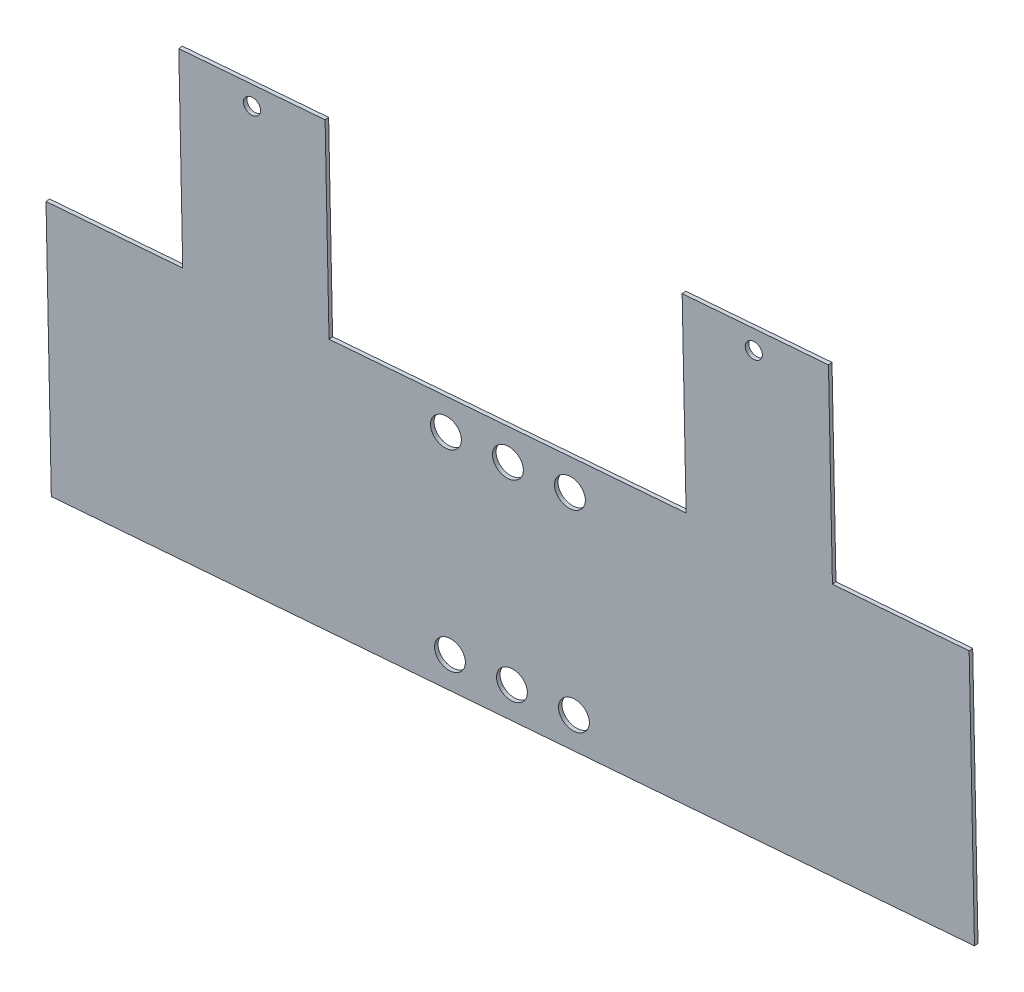
SolidWorks part; units mm, degrees
ref_plane "Front Plane" through (0, 0, 0) normal (0, 0, 1) x (1, 0, 0)
ref_plane "Top Plane" through (0, 0, 0) normal (0, 1, 0) x (1, 0, 0)
ref_plane "Right Plane" through (0, 0, 0) normal (1, 0, 0) x (0, 0, -1)
sketch "Sketch1" plane through (16.9972, -4.1499, 204.6314) normal (-0.0828, 0.0202, -0.9964) x (0.9966, 0.002, -0.0827)
  line L0 (-405.6316, 283.217) -> (-385.6926, 283.217)
  line L1 (-520.3126, 323.857) -> (-500.3736, 323.857)
  line L2 (-520.3126, 323.857) -> (-520.3126, 283.217)
  line L3 (-520.3126, 283.217) -> (-500.3736, 283.217)
  line L4 (-385.6926, 323.857) -> (-385.6926, 283.217)
  line L6 (-426.9676, 283.217) -> (-426.9676, 253.0016)
  line L7 (-426.9676, 253.0016) -> (-405.6316, 253.0016)
  line L8 (-405.6316, 283.217) -> (-405.6316, 253.0016)
  line L9 (-405.0144, 323.857) -> (-385.6926, 323.857)
  line L14 (-479.4985, 323.857) -> (-465.3599, 323.857)
  line L20 (-500.3736, 283.217) -> (-500.3736, 253.0016)
  line L21 (-500.3736, 253.0016) -> (-479.0376, 253.0016)
  line L22 (-479.0376, 283.217) -> (-479.0376, 253.0016)
  line L23 (-479.0376, 283.217) -> (-426.9676, 283.217)
  line L24 (-432.4144, 323.857) -> (-405.0144, 323.857)
  line L25 (-500.3736, 323.857) -> (-479.4985, 323.857)
  line L26 (-445.0971, 323.857) -> (-432.4144, 323.857)
  line L31 (-465.3599, 323.857) -> (-445.0971, 323.857)
  dimension "D1" = 134.62
  dimension "D2" = 40.64
  dimension "D3" = 21.336
  dimension "D4" = 52.07
extrude "Boss-Extrude1" add sketch "Sketch1" along normal blind 0.6096
ref_plane "Plane1" through (-508.5923, -1, 42.2247) normal (0.9966, 0.002, -0.0827) x (-0.0828, 0.028, -0.9962)
sketch "Sketch5" plane through (16.9468, -4.1376, 204.024) normal (-0.0828, 0.0202, -0.9964) x (-0.9966, -0.0017, 0.0827)
  circle A0 centre (461.9962, -318.9871) radius 2.25
  circle A1 centre (452.9566, -318.9845) radius 2.25
  circle A2 centre (443.9171, -318.982) radius 2.25
  dimension "D1" = 4.5
extrude "Cut-Extrude2" cut sketch "Sketch5" against normal up to surface (0.6096 mm away) up to face at (-434.3727, -284.8984, 236.4298)
ref_plane "Plane2" through (0.0852, -303.4744, -6.1615) normal (0.0003, -0.9998, -0.0203) x (-1, -0.0003, 0)
mirror "Mirror1" about plane through (0.0852, -303.4744, -6.1615) normal (0.0003, -0.9998, -0.0203) of "Cut-Extrude2"
sketch "Sketch6" plane through (16.9468, -4.1376, 204.024) normal (-0.0828, 0.0202, -0.9964) x (-0.9966, -0.0017, 0.0827)
  circle A1 centre (416.5068, -256.1738) radius 1.25
  dimension "D1" = 2.5
extrude "Cut-Extrude5" cut sketch "Sketch6" against normal up to surface (0.6096 mm away) up to face at (-445.6649, -293.213, 237.1991)
ref_plane "Plane3" through (-451.4485, -0.8877, 37.4805) normal (-0.9966, -0.002, 0.0827) x (0.0827, 0.0002, 0.9966)
sketch "Sketch7" plane through (16.9468, -4.1376, 204.024) normal (-0.0828, 0.0202, -0.9964) x (-0.9966, -0.0017, 0.0827)
  circle A0 centre (489.6815, -256.1944) radius 1.25
extrude "Cut-Extrude6" cut sketch "Sketch7" against normal up to surface (0.6096 mm away) up to face at (-399.3264, -260.97, 234.004)
